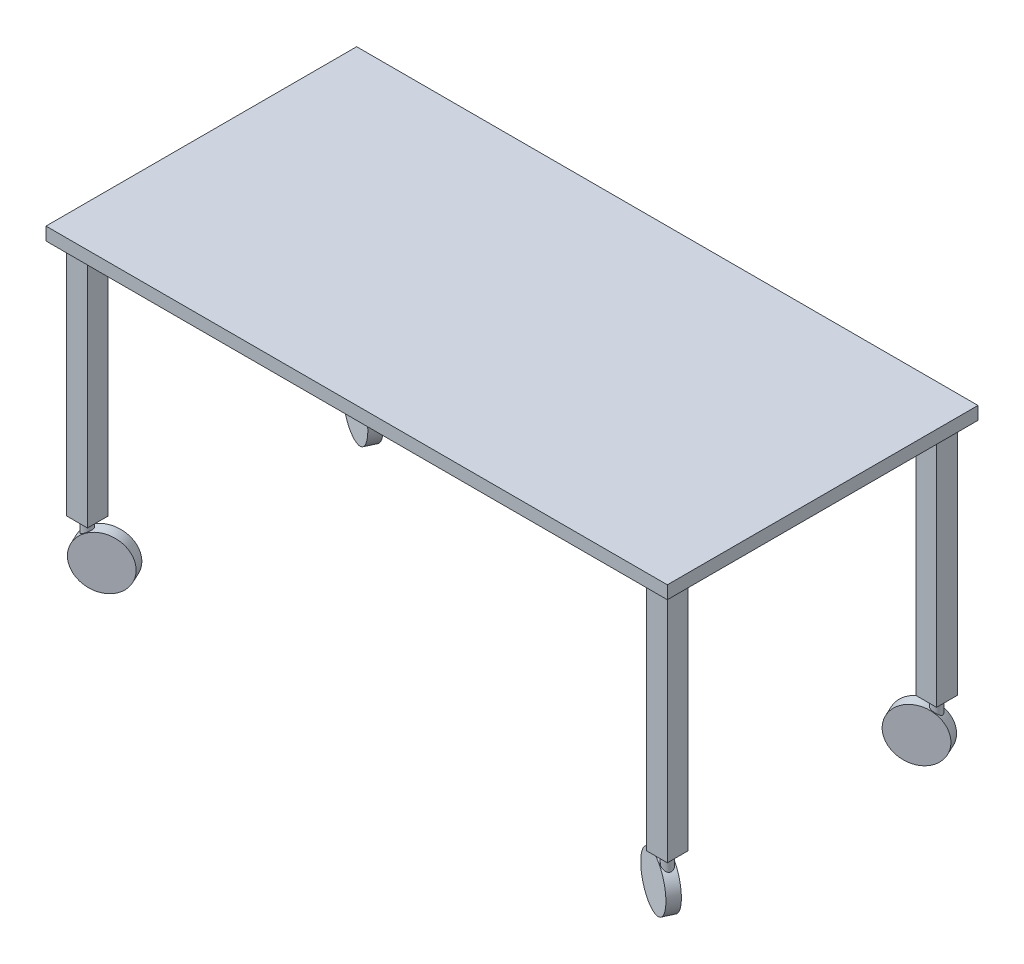
SolidWorks part; units mm, degrees
material "Plain Carbon Steel"
ref_plane "Front Plane" through (0, 0, 0) normal (0, 0, 1) x (1, 0, 0)
ref_plane "Top Plane" through (0, 0, 0) normal (0, 1, 0) x (1, 0, 0)
ref_plane "Right Plane" through (0, 0, 0) normal (1, 0, 0) x (0, 0, -1)
sketch "Sketch1" plane through (0, 0, 0) normal (0, 1, 0) x (1, 0, 0)
  line L1 (-762, -381) -> (762, -381)
  line L2 (-762, -381) -> (-762, 381)
  line L3 (-762, 381) -> (762, 381)
  line L4 (762, -381) -> (762, 381)
  line L5 (-762, -381) -> (762, 381) construction
  line L6 (-762, 381) -> (762, -381) construction
  point P0 (0, 0)
  dimension "D1" = 1524
  dimension "D2" = 762
extrude "Boss-Extrude1" add sketch "Sketch1" against normal blind 31.75
sketch "Sketch2" plane through (0, -31.75, 0) normal (0, -1, 0) x (1, 0, 0)
  line L0 (762, 381) -> (762, -381) construction
  line L1 (-736.6, -355.6) -> (736.6, -355.6) construction
  line L2 (-736.6, -355.6) -> (-736.6, 355.6) construction
  line L3 (-736.6, 355.6) -> (736.6, 355.6) construction
  line L4 (736.6, -355.6) -> (736.6, 355.6) construction
  line L5 (-736.6, -355.6) -> (736.6, 355.6) construction
  line L6 (-736.6, 355.6) -> (736.6, -355.6) construction
  line L7 (-736.6, 355.6) -> (-685.8, 355.6)
  line L8 (-736.6, 355.6) -> (-736.6, 304.8)
  line L9 (-736.6, 304.8) -> (-685.8, 304.8)
  line L10 (-685.8, 355.6) -> (-685.8, 304.8)
  line L11 (-736.6, -355.6) -> (-685.8, -355.6)
  line L12 (-736.6, -355.6) -> (-736.6, -304.8)
  line L13 (-736.6, -304.8) -> (-685.8, -304.8)
  line L14 (-685.8, -355.6) -> (-685.8, -304.8)
  line L15 (736.6, -355.6) -> (685.8, -355.6)
  line L16 (736.6, -355.6) -> (736.6, -304.8)
  line L17 (736.6, -304.8) -> (685.8, -304.8)
  line L18 (685.8, -355.6) -> (685.8, -304.8)
  line L19 (736.6, 355.6) -> (685.8, 355.6)
  line L20 (736.6, 355.6) -> (736.6, 304.8)
  line L21 (736.6, 304.8) -> (685.8, 304.8)
  line L22 (685.8, 355.6) -> (685.8, 304.8)
  line L23 (-762, 381) -> (762, 381) construction
  point P0 (0, 0)
  dimension "D1" = 50.8
  dimension "D2" = 50.8
  dimension "D3" = 25.4
  dimension "D4" = 25.4
extrude "Boss-Extrude2" add sketch "Sketch2" along normal blind 584.2
sketch "Sketch3" plane through (0, -615.95, 0) normal (0, -1, 0) x (1, 0, 0)
  line L1 (-711.2, -330.2) -> (711.2, -330.2) construction
  line L2 (-711.2, -330.2) -> (-711.2, 330.2) construction
  line L3 (-711.2, 330.2) -> (711.2, 330.2) construction
  line L4 (711.2, -330.2) -> (711.2, 330.2) construction
  line L5 (-711.2, -330.2) -> (711.2, 330.2) construction
  line L6 (-711.2, 330.2) -> (711.2, -330.2) construction
  line L7 (685.8, 355.6) -> (736.6, 304.8) construction
  circle A0 centre (711.2, 330.2) radius 12.7
  circle A1 centre (711.2, -330.2) radius 12.7
  circle A2 centre (-711.2, -330.2) radius 12.7
  circle A3 centre (-711.2, 330.2) radius 12.7
  point P4 (0, 0)
  point P6 (685.8, 330.2)
  point P8 (0, 0)
  point P9 (0, 0)
  point P13 (711.2, 330.2)
  dimension "D1" = 25.4
extrude "Boss-Extrude3" add sketch "Sketch3" along normal blind 101.6
ref_axis "Axis1" through (711.2, -717.55, 330.2) along (0, 1, 0)
ref_axis "Axis2" through (0, 35.8775, 0) along (0, -1, 0)
ref_plane "Plane1" through (0, 0, 0) normal (-0.4211, 0, 0.907) x (0.907, 0, 0.4211)
sketch "Sketch4" plane through (0, 0, 0) normal (-0.4211, 0, 0.907) x (0.907, 0, 0.4211)
  line L0 (784.1157, -717.55) -> (784.1157, -615.95) construction
  circle A0 centre (752.3657, -698.5) radius 63.5
  point P4 (752.3657, -762)
  dimension "D2" = 127
  dimension "D1" = 31.75
  dimension "D3" = 762
extrude "Boss-Extrude4" add sketch "Sketch4" along normal mid plane 28.575
mirror "Mirror1" about plane through (0, 0, 0) normal (0, 0, 1) of "Boss-Extrude4"
mirror "Mirror2" about plane through (0, 0, 0) normal (1, 0, 0) of "Boss-Extrude4", "Mirror1"
